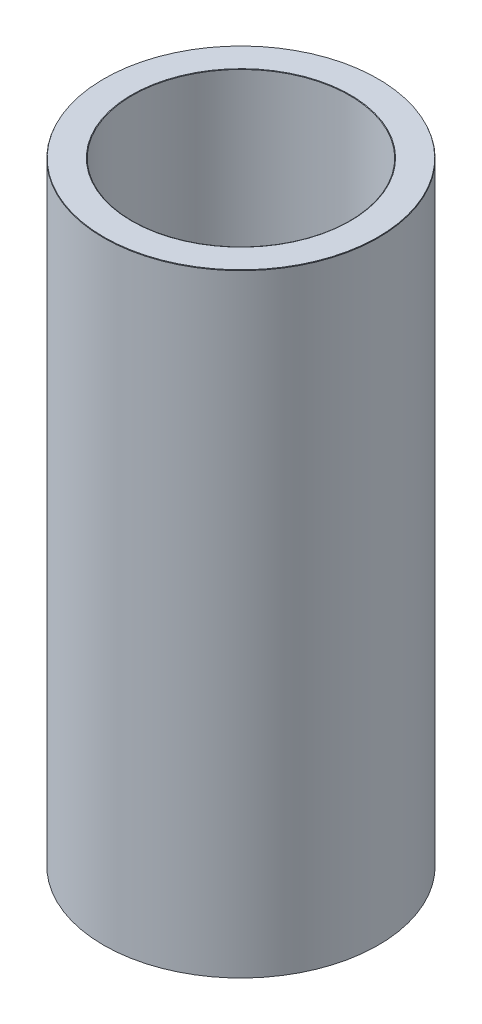
SolidWorks part; units mm, degrees
ref_plane "Front Plane" through (0, 0, 0) normal (0, 0, 1) x (1, 0, 0)
ref_plane "Top Plane" through (0, 0, 0) normal (0, 1, 0) x (1, 0, 0)
ref_plane "Right Plane" through (0, 0, 0) normal (1, 0, 0) x (0, 0, -1)
sketch "Sketch1" plane through (0, 0, 0) normal (0, 1, 0) x (1, 0, 0)
  circle A0 centre (0, 0) radius 57.5
  dimension "SLEEVE_OD" = 115
extrude "Boss-Extrude1" add sketch "Sketch1" along normal blind 256.8521
sketch "Sketch2" plane through (0, 0, 0) normal (0, 1, 0) x (1, 0, 0)
  circle A0 centre (0, 0) radius 45.5343
  dimension "BORE_D" = 91.0687
extrude "Cut-Extrude1" cut sketch "Sketch2" along normal through all
chamfer "Chamfer1" distance 0.2456 angle 24.412 4 edges at (0, 256.8521, 45.5343) (0, 0, 45.5343) (0, 0, 57.5) (0, 256.8521, 57.5) first distance on face at (0, 256.8521, 45.5343) first distance on face at (0, 0, 45.5343) first distance on face at (0, 256.8521, 57.5)
